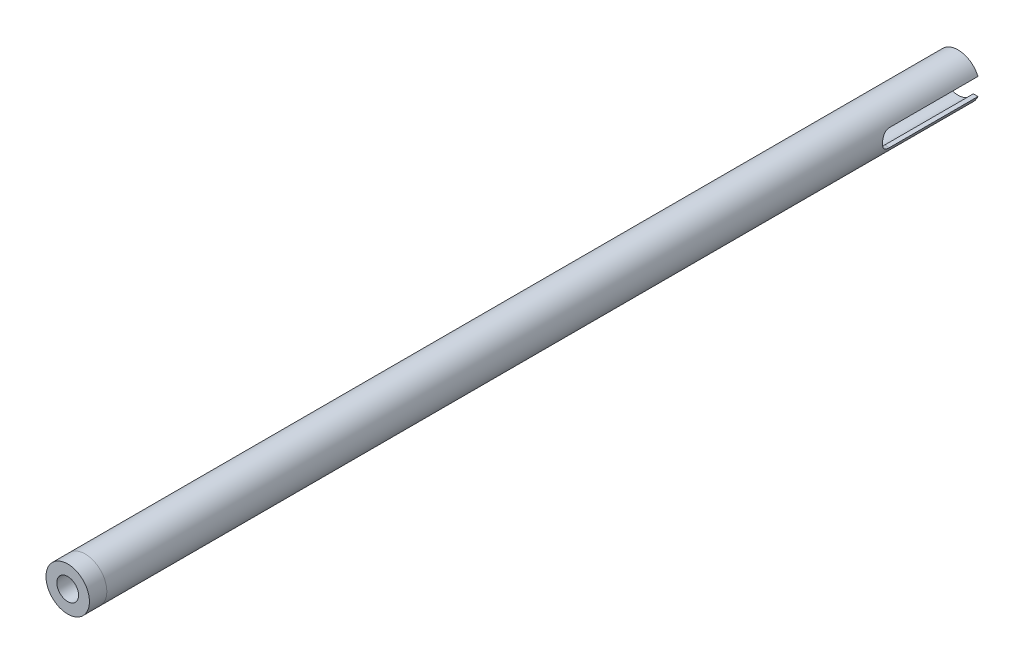
SolidWorks part; units mm, degrees
ref_plane "Front Plane" through (0, 0, 0) normal (0, 0, 1) x (1, 0, 0)
ref_plane "Top Plane" through (0, 0, 0) normal (0, 1, 0) x (1, 0, 0)
ref_plane "Right Plane" through (0, 0, 0) normal (1, 0, 0) x (0, 0, -1)
sketch "Axis" plane through (0, 0, 0) normal (0, 1, 0) x (1, 0, 0)
  line L0 (0, 0) -> (0, 325.114) construction
  line L1 (0, 0) -> (0, -34.925) construction
  line L2 (0, 325.114) -> (-7.9375, 325.114) construction
  line L3 (0, 354.4828) -> (-10.3187, 316.3034) construction
  dimension "D1" = 34.925
  dimension "D2" = 7.9375
sketch "Sketch1" plane through (0, 0, 0) normal (0, 0, 1) x (1, 0, 0)
  line L0 (-7.9375, 0) -> (7.9375, 0) construction
  line L1 (-7.2748, 3.175) -> (7.2748, 3.175)
  line L2 (-7.2748, -3.175) -> (7.2748, -3.175)
  circle A0 centre (0, 0) radius 7.9375
  circle A1 centre (0, 0) radius 6.4135
  circle A2 centre (0, 0) radius 3.9688
  dimension "D1" = 15.875
  dimension "D3" = 7.9375
  dimension "D2" = 1.524
  dimension "D4" = 6.35
extrude "Threaded insert 1-1" add sketch "Sketch1" against normal blind 6.35 contours A2 L1 A1 | A1 L1 A0 | A2 L0 A1 L1 | A1 L0 A0 L1 | L0 A1 L2 A0 | L0 A2 L2 A1 | A2 L2 A1 | A1 L2 A0 | L0 A1 L2 A2 | L0 A0 L2 A1 | A0 L0 A1 L1 | A1 L0 A2 L1 region at (4.7887, 1.6543, 0) region at (4.7887, -1.6543, 0) region at (6.9234, 1.6163, 0) region at (6.9234, -1.6163, 0) region at (-4.7887, -1.6543, 0) region at (-4.7887, 1.6543, 0) region at (0, 4.6159, 0) region at (0, -4.6159, 0) region at (0, 6.5666, 0) region at (6.4237, -3.3281, 0) region at (-6.9234, -1.6163, 0) region at (-6.9234, 1.6163, 0)
extrude "Threaded insert 1-2" add sketch "Sketch1<3>" against normal blind 9.525 from surface contours A2 L1 A1 | A2 L0 A1 L1 | L0 A2 L2 A1 | A2 L2 A1 | L0 A1 L2 A2 | A1 L0 A2 L1 region at (4.7887, 1.6543, 0) region at (4.7887, -1.6543, 0) region at (-4.7887, -1.6543, 0) region at (-4.7887, 1.6543, 0) region at (0, 4.6159, 0) region at (0, -4.6159, 0) starting at face at (7.9375, 0, -6.35)
sketch "Sketch1<3>" plane through (0, 0, 0) normal (0, 0, 1) x (1, 0, 0) same geometry as "Sketch1"
extrude "A-arm tube" add sketch "Sketch1<4>" against normal up to vertex (325.114 mm away) from surface separate body contours A1 L1 A0 | A1 L0 A0 L1 | L0 A1 L2 A0 | A1 L2 A0 | L0 A0 L2 A1 | A0 L0 A1 L1 region at (6.9234, 1.6163, 0) region at (6.9234, -1.6163, 0) region at (0, 6.5666, 0) region at (6.4237, -3.3281, 0) region at (-6.9234, -1.6163, 0) region at (-6.9234, 1.6163, 0) up to point (0, 0, -325.114) starting at face at (6.4135, 0, -6.35)
sketch "Sketch1<4>" plane through (0, 0, 0) normal (0, 0, 1) x (1, 0, 0) same geometry as "Sketch1"
extrude "Apex slot" cut sketch "Sketch1<5>" along normal blind 35.56 from surface contours A0 L0 A1 L1 | L0 A0 L2 A1 | A1 L0 A0 L1 | L0 A1 L2 A0 region at (6.9234, 1.6163, 0) region at (6.9234, -1.6163, 0) region at (-6.9234, -1.6163, 0) region at (-6.9234, 1.6163, 0) starting at face at (6.4135, 0, -325.114)
sketch "Sketch1<5>" plane through (0, 0, 0) normal (0, 0, 1) x (1, 0, 0) same geometry as "Sketch1"
fillet "Fillet1" radius 3.175 4 edges at (-6.4237, 3.175, -289.554) (-6.4237, -3.175, -289.554) (6.4237, -3.175, -289.554) (6.4237, 3.175, -289.554)
equation "\"tube diameter\"= 5 / 8"
equation "\"tube thickness\"= .06"
equation "\"apex thickness\"= .25"
equation "\"tube slot\"= 1.4"
equation "\"D1@Sketch1\"=\"tube diameter\""
equation "\"D2@Sketch1\"=\"tube thickness\""
equation "\"threaded insert hole\"= .3125"
equation "\"D3@Sketch1\"=\"threaded insert hole\""
equation "\"D4@Sketch1\"=\"apex thickness\""
equation "\"D1@Apex slot\" = \"tube slot\""
equation "\"D1@Fillet1\"=\"apex thickness\"/2"
equation "\"D2@Axis\"=\"tube diameter\"/2"
